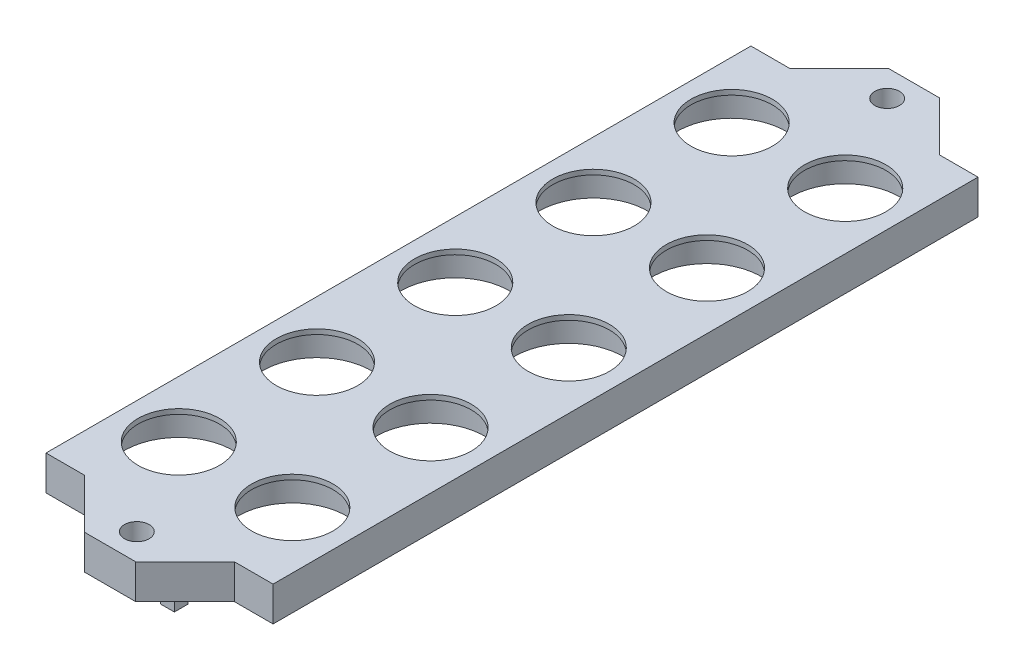
SolidWorks part; units mm, degrees
ref_plane "Front Plane" through (0, 0, 0) normal (0, 0, 1) x (1, 0, 0)
ref_plane "Top Plane" through (0, 0, 0) normal (0, 1, 0) x (1, 0, 0)
ref_plane "Right Plane" through (0, 0, 0) normal (1, 0, 0) x (0, 0, -1)
sketch "Szkic1" plane through (0, 0, 0) normal (0, 1, 0) x (1, 0, 0)
  line L0 (6.5, 25) -> (-3.5, 15)
  line L1 (-11.5, 15) -> (34.5, 15)
  line L2 (-11.5, 15) -> (-11.5, -127)
  line L3 (-11.5, -127) -> (34.5, -127)
  line L4 (34.5, 15) -> (34.5, -127)
  line L5 (6.5, 15) -> (16.5, 15)
  line L6 (6.5, 15) -> (6.5, 25)
  line L7 (6.5, 25) -> (16.5, 25)
  line L8 (16.5, 15) -> (16.5, 25)
  line L9 (16.5, 25) -> (26.5, 15)
  line L12 (-11.5, -56) -> (-33.554, -56) construction
  line L13 (16.5, -137) -> (26.5, -127)
  line L14 (16.5, -127) -> (16.5, -137)
  line L15 (6.5, -127) -> (6.5, -137)
  line L16 (6.5, -137) -> (16.5, -137)
  line L17 (6.5, -137) -> (-3.5, -127)
  line L18 (-11.5, -155) -> (34.5, -155) [skipped]
  line L19 (-11.5, -183) -> (34.5, -183) [skipped]
  circle A0 centre (0, 0) radius 8.25
  circle A1 centre (0, 0) radius 10.6
  circle A2 centre (0, 0) radius 10.1
  circle A3 centre (0, 0) radius 11
  circle A5 centre (23, 0) radius 8.25
  circle A6 centre (23, 0) radius 10.6
  circle A7 centre (23, 0) radius 10.1
  circle A8 centre (23, 0) radius 11
  circle A10 centre (23, -28) radius 8.25
  circle A11 centre (23, -28) radius 10.6
  circle A12 centre (23, -28) radius 10.1
  circle A13 centre (23, -28) radius 11
  circle A15 centre (0, -28) radius 8.25
  circle A16 centre (0, -28) radius 10.6
  circle A17 centre (0, -28) radius 10.1
  circle A18 centre (0, -28) radius 11
  circle A20 centre (0, -56) radius 11
  circle A21 centre (0, -56) radius 10.6
  circle A22 centre (0, -56) radius 10.1
  circle A23 centre (0, -56) radius 8.25
  circle A24 centre (23, -56) radius 8.25
  circle A25 centre (23, -56) radius 10.1
  circle A26 centre (23, -56) radius 10.6
  circle A27 centre (23, -56) radius 11
  circle A28 centre (0, -84) radius 11
  circle A29 centre (0, -84) radius 10.6
  circle A30 centre (0, -84) radius 10.1
  circle A31 centre (0, -84) radius 8.25
  circle A32 centre (23, -84) radius 8.25
  circle A33 centre (23, -84) radius 10.1
  circle A34 centre (23, -84) radius 10.6
  circle A35 centre (23, -84) radius 11
  circle A36 centre (0, -112) radius 11
  circle A37 centre (0, -112) radius 10.6
  circle A38 centre (0, -112) radius 10.1
  circle A39 centre (0, -112) radius 8.25
  circle A40 centre (23, -112) radius 8.25
  circle A41 centre (23, -112) radius 10.1
  circle A42 centre (23, -112) radius 10.6
  circle A43 centre (23, -112) radius 11
  dimension "D1" = 16.5
  dimension "D2" = 20.2
  dimension "D3" = 21.2
  dimension "D4" = 0.4
  dimension "D5" = 23
  dimension "D8" = 11.5
  dimension "D10" = 2
  dimension "D9" = 11.5
  dimension "D11" = 15
  dimension "D12" = 10
  dimension "D13" = 18
  dimension "D14" = 10
  dimension "D15" = 3
  dimension "D16" = 15
  dimension "D17" = 45
  dimension "D18" = 45
  dimension "D6" = 2
  dimension "D7" = 2
extrude "Dodanie-wyciągnięcie1" add sketch "Szkic1" along normal blind 1 contours L4 L1 L2 | L4 L2 | L2 L3 L4 | A18 | A18 A16 | A16 A17 | A17 A15 | A12 A10 | A11 A12 | A13 A11 | A13 | A7 A5 | A6 A7 | A8 A6 | A8 | A3 | A3 A1 | A1 A2 | A2 A0 | L1 L6 L0 | L1 L8 L7 L6 | L9 L8 L1 | A22 A23 | A21 A22 | A20 A21 | A25 A24 | A26 A25 | A27 A26 | A33 A32 | A34 A33 | A35 A34 | A28 A29 | A29 A30 | A30 A31 | A41 A40 | A42 A41 | A43 A42 | A38 A39 | A37 A38 | A36 A37 | L15 L16 L14 L3 | L17 L15 L3 | L3 L14 L13 region at (3.1667, 0, -18.3333) region at (11.5, 0, -20) region at (11.5, 0, 56) region at (19.8333, 0, -18.3333) region at (3.1667, 0, 130.3333) region at (11.5, 0, 132) region at (19.8333, 0, 130.3333) region at (-10.3002, 0, 0) region at (-9.8143, 0, 0) region at (-10.6889, 0, 0) region at (12.6998, 0, 0) region at (13.1857, 0, 0) region at (12.3111, 0, 0) region at (12.6998, 0, 28) region at (13.1857, 0, 28) region at (12.3111, 0, 28) region at (-10.3002, 0, 28) region at (-9.8143, 0, 28) region at (-10.6889, 0, 28) region at (-10.6889, 0, 56) region at (-10.3002, 0, 56) region at (-9.8143, 0, 56) region at (13.1857, 0, 56) region at (12.6998, 0, 56) region at (12.3111, 0, 56) region at (-10.6889, 0, 84) region at (-10.3002, 0, 84) region at (-9.8143, 0, 84) region at (13.1857, 0, 84) region at (12.6998, 0, 84) region at (12.3111, 0, 84) region at (-10.6889, 0, 112) region at (-10.3002, 0, 112) region at (-9.8143, 0, 112) region at (13.1857, 0, 112) region at (12.6998, 0, 112) region at (12.3111, 0, 112)
extrude "Dodanie-wyciągnięcie2" add sketch "Szkic1<3>" against normal blind 6 from surface contours A3 | A8 | L4 L1 L2 | L4 L2 | A18 | A13 | L2 L3 L4 | L1 L6 L0 | L1 L8 L7 L6 | L9 L8 L1 | L17 L15 L3 | L15 L16 L14 L3 | L3 L14 L13 region at (3.1667, 0, -18.3333) region at (11.5, 0, -20) region at (11.5, 0, 56) region at (19.8333, 0, -18.3333) region at (3.1667, 0, 130.3333) region at (11.5, 0, 132) region at (19.8333, 0, 130.3333) starting at face at (11.5, 0, 56)
sketch "Szkic1<3>" plane through (0, 0, 0) normal (0, 1, 0) x (1, 0, 0) same geometry as "Szkic1"
sketch "Szkic2" plane through (0, 1, 0) normal (0, 1, 0) x (1, 0, 0)
  line L0 (-11.5, 15) -> (34.5, 15)
  line L1 (11.5, 15) -> (11.5, 25)
  line L2 (6.5, 25) -> (16.5, 25) construction
  line L3 (-11.5, -56) -> (34.5, -56) construction
  line L4 (-11.5, 15) -> (-11.5, -127) construction
  line L5 (34.5, 15) -> (34.5, -127) construction
  circle A0 centre (11.5, 20) radius 2.5
  circle A1 centre (11.5, -132) radius 2.5
  dimension "D1" = 5
extrude "Wytnij-wyciągnięcie1" cut sketch "Szkic2" against normal blind 20 contours L1 A0 | L1 A0 | A1 region at (10.439, 1, -20) region at (12.561, 1, -20) region at (11.5, 1, 132)
sketch "Szkic5" plane through (0, 1, 0) normal (0, 1, 0) x (1, 0, 0)
  line L0 (-3.5, 15) -> (6.5, 25)
  line L1 (6.5, 25) -> (16.5, 25)
  line L2 (16.5, 25) -> (26.5, 15)
  line L3 (26.5, 15) -> (-3.5, 15)
  line L4 (-11.5, -56) -> (-35.7115, -56) construction
  line L5 (-11.5, 15) -> (-11.5, -127) construction
  line L6 (26.5, -127) -> (-3.5, -127)
  line L7 (16.5, -137) -> (26.5, -127)
  line L8 (6.5, -137) -> (16.5, -137)
  line L9 (-3.5, -127) -> (6.5, -137)
  circle A0 centre (11.5, 20) radius 2
  circle A1 centre (11.5, -132) radius 2
  circle A2 centre (11.5, -132) radius 4.05
  circle A3 centre (11.5, 20) radius 4.05
  circle M2 centre (11.5, -132) radius 2.5
  circle M25 centre (11.5, 20) radius 2.5
  dimension "D1" = 8.1
  dimension "D2" = 8.1
extrude "Wytnij-wyciągnięcie2" [suppressed] cut sketch "Szkic5" along normal blind 1 from surface contours A2 M2 | A3 M25
sketch "Szkic6" plane through (0, 1, 0) normal (0, 1, 0) x (1, 0, 0)
  line L0 (-3.5, 15) -> (6.5, 25)
  line L1 (6.5, 25) -> (16.5, 25)
  line L2 (16.5, 25) -> (26.5, 15)
  line L3 (-11.5, 15) -> (-3.5, 15)
  line L4 (26.5, 15) -> (34.5, 15)
  line L5 (34.5, 15) -> (34.5, 15.4)
  line L6 (34.5, 15.4) -> (26.6657, 15.4)
  line L7 (26.6657, 15.4) -> (16.6657, 25.4)
  line L8 (16.6657, 25.4) -> (6.3343, 25.4)
  line L9 (6.3343, 25.4) -> (-3.6657, 15.4)
  line L10 (-3.6657, 15.4) -> (-11.5, 15.4)
  line L11 (-11.5, 15.4) -> (-11.5, 15)
  line L12 (34.5, -56) -> (44.0017, -56)
  line L13 (34.5, 15) -> (34.5, -127) construction
  line L14 (-11.5, -127.4) -> (-11.5, -127)
  line L15 (-3.6657, -127.4) -> (-11.5, -127.4)
  line L16 (6.3343, -137.4) -> (-3.6657, -127.4)
  line L17 (16.6657, -137.4) -> (6.3343, -137.4)
  line L18 (26.6657, -127.4) -> (16.6657, -137.4)
  line L19 (34.5, -127.4) -> (26.6657, -127.4)
  line L20 (34.5, -127) -> (34.5, -127.4)
  line L21 (26.5, -127) -> (34.5, -127)
  line L22 (-11.5, -127) -> (-3.5, -127)
  line L23 (16.5, -137) -> (26.5, -127)
  line L24 (6.5, -137) -> (16.5, -137)
  line L25 (-3.5, -127) -> (6.5, -137)
  dimension "D1" = 0.4
  dimension "D2" = 0.4
  dimension "D3" = 0.4
  dimension "D4" = 0.4
  dimension "D5" = 0.4
extrude "Dodanie-wyciągnięcie3" add sketch "Szkic6" against normal up to surface (7 mm away) contours L24 L23 L21 L20 L19 L18 L17 L16 L15 L14 L22 L25 | L1 L2 L4 L5 L6 L7 L8 L9 L10 L11 L3 L0 up to face at (11.5, -6, 129.5)
sketch "Szkic7" plane through (0, -6, 0) normal (0, -1, 0) x (1, 0, 0)
  line L0 (16.6657, -25.4) -> (6.3343, -25.4) construction
  line L1 (3.6, -17.5) -> (6.4, -17.5)
  line L2 (3.6, -17.5) -> (3.6, -20.3)
  line L3 (3.6, -20.3) -> (6.4, -20.3)
  line L4 (6.4, -17.5) -> (6.4, -20.3)
  line L5 (-11.5, 127.4) -> (-11.5, -15.4) construction
  line L6 (11.5, -25.4) -> (11.5, -28.2248)
  line L7 (16.6, -17.5) -> (16.6, -20.3)
  line L8 (19.4, -20.3) -> (16.6, -20.3)
  line L9 (19.4, -17.5) -> (19.4, -20.3)
  line L10 (19.4, -17.5) -> (16.6, -17.5)
  line L11 (-11, 56) -> (-24.1504, 56)
  line L20 (19.4, 129.5) -> (16.6, 129.5)
  line L21 (19.4, 129.5) -> (19.4, 132.3)
  line L22 (19.4, 132.3) -> (16.6, 132.3)
  line L23 (16.6, 129.5) -> (16.6, 132.3)
  line L24 (6.4, 129.5) -> (6.4, 132.3)
  line L25 (3.6, 132.3) -> (6.4, 132.3)
  line L26 (3.6, 129.5) -> (3.6, 132.3)
  line L27 (3.6, 129.5) -> (6.4, 129.5)
  circle A0 centre (0, 56) radius 11 construction
  circle A1 centre (0, 56) radius 11 construction
  point P28 (5, -18.9)
  point P29 (0, 0)
  point P30 (5, 130.9)
  point P31 (4.5964, -19.0432)
  dimension "D1" = 2.8
  dimension "D2" = 2.8
  dimension "D3" = 1.4
  dimension "D4" = 1.4
  dimension "D5" = 6.5
  dimension "D6" = 16.5
extrude "Dodanie-wyciągnięcie4" add sketch "Szkic7" along normal blind 3 contours L9 L10 L7 L8 | L4 L1 L2 L3 | L23 L20 L21 L22 | L26 L27 L24 L25 region at (5, -6, -18.9) region at (18, -6, -18.9) region at (18, -6, 130.9) region at (5, -6, 130.9)
sketch "Szkic8" plane through (0, -6, 0) normal (0, -1, 0) x (1, 0, 0)
  line L0 (-3.6657, 127.4) -> (26.6657, 127.4)
  line L1 (26.6657, 127.4) -> (16.6657, 137.4)
  line L2 (16.6657, 137.4) -> (6.3343, 137.4)
  line L3 (6.3343, 137.4) -> (-3.6657, 127.4)
  line L5 (3.6, 129.5) -> (6.4, 129.5)
  line L6 (3.6, 129.5) -> (3.6, 132.3)
  line L7 (3.6, 132.3) -> (6.4, 132.3)
  line L8 (6.4, 129.5) -> (6.4, 132.3)
  line L9 (16.6, 129.5) -> (19.4, 129.5)
  line L10 (16.6, 129.5) -> (16.6, 132.3)
  line L11 (16.6, 132.3) -> (19.4, 132.3)
  line L12 (19.4, 129.5) -> (19.4, 132.3)
  circle A0 centre (11.5, 132) radius 2.5
